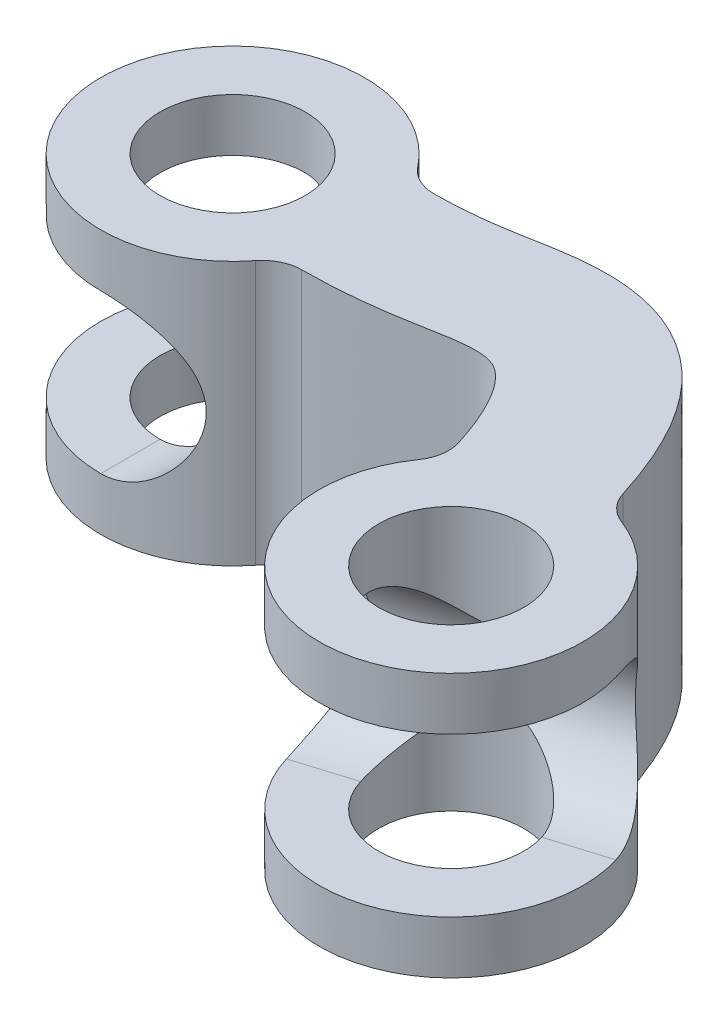
SolidWorks part; units mm, degrees
ref_plane "Front Plane" through (0, 0, 0) normal (0, 0, 1) x (1, 0, 0)
ref_plane "Top Plane" through (0, 0, 0) normal (0, 1, 0) x (1, 0, 0)
ref_plane "Right Plane" through (0, 0, 0) normal (1, 0, 0) x (0, 0, -1)
sketch "Sketch5" plane through (0, 0, 0) normal (0, 1, 0) x (1, 0, 0)
  line L0 (0, 0) -> (20, 0) construction
  line L1 (18.2322, -1.7678) -> (14.6967, 1.7678) construction
  line L2 (0, 0) -> (5, 0) construction
  line L3 (18.7059, 4.8296) -> (18.2322, 5.3033)
  line L4 (15.1704, 1.2941) -> (14.6967, 1.7678)
  line L5 (5, 2.5) -> (4.3301, 2.5)
  line L6 (5, -2.5) -> (4.3301, -2.5)
  line L7 (21.7678, 1.7678) -> (18.2322, 5.3033) construction
  line L8 (20, 0) -> (16.4645, 3.5355) construction
  line L9 (20, 0) -> (16.4645, 3.5355) construction
  line L10 (20, 0) -> (16.4645, -3.5355) construction
  arc A0 (4.3301, 2.5) -> (4.3301, -2.5) centre (0, 0) ccw
  arc A1 (15.1704, 1.2941) -> (18.7059, 4.8296) centre (20, 0) ccw
  spline S0 degree 3 poles (5, 0) (7.2923, 0) (9.8659, 3.8705) (14.4742, 5.5258) (16.4645, 3.5355) knots 0 0 0 0 0.526061 1 1 1 1 construction
  spline S1 degree 1 poles (5, 2.5) (18.2322, 5.3033) knots 0 0 1 1 construction
  spline S2 degree 3 poles (5, 2.5) (5.1773, 2.5) (5.4681, 2.5503) (6.2162, 2.992) (7.2869, 3.9461) (8.6553, 5.2032) (10.471, 6.4596) (12.7733, 7.3462) (15.206, 7.2299) (17.0379, 6.3484) (17.863, 5.6725) (18.2322, 5.3033) knots 0 0 0 0 0.125 0.25 0.375 0.5 0.625 0.75 0.875 0.9375 1 1 1 1
  spline S3 degree 1 poles (5, -2.5) (14.6967, 1.7678) knots 0 0 1 1 construction
  spline S4 degree 3 poles (5, -2.5) (5.4364, -2.5) (6.3305, -2.4036) (7.8897, -1.8868) (9.3956, -0.8905) (10.7305, 0.3262) (11.849, 1.3378) (12.8808, 2.0258) (13.5619, 2.2438) (13.8761, 2.2489) (14.0574, 2.2149) (14.2613, 2.1231) (14.4834, 1.9668) (14.6318, 1.8327) (14.6967, 1.7678) knots 0 0 0 0 0.0625 0.125 0.25 0.375 0.5 0.625 0.75 0.8125 0.875 0.9375 0.96875 1 1 1 1
  dimension "D2" = 10
  dimension "D3" = 10
  dimension "D1" = 20
  dimension "D4" = 5
  dimension "D5" = 2.5
  dimension "D6" = 2.5
  dimension "D7" = 10.5631
  dimension "D8" = 3.4592
  dimension "D9" = 14.6967
  dimension "D10" = 16.4645
  dimension "D11" = 3.5355
  dimension "D12" = 45
  dimension "D13" = 45
extrude "Boss-Extrude3" [suppressed] add sketch "Sketch5" along normal blind 10
sketch "Sketch6" [suppressed] plane through (0, 0, 0) normal (0, 1, 0) x (1, 0, 0)
  circle A0 centre (0, 0) radius 2.75
  circle A1 centre (20, 0) radius 2.75
  arc A2 (4.3301, 2.5) -> (4.3301, -2.5) centre (0, 0) ccw construction
  arc A3 (15.1704, 1.2941) -> (18.7059, 4.8296) centre (20, 0) ccw construction
  dimension "D1" = 5.5
  dimension "D2" = 5.5
extrude "Cut-Extrude3" [suppressed] cut sketch "Sketch6" along normal up to next
sketch "Sketch8" [suppressed] plane through (0, 0, 0) normal (0, 0, 1) x (1, 0, 0)
  line L0 (0, 0) -> (0, 10) construction
  line L1 (2.75, 10) -> (-2.75, 10) construction
  line L2 (20, 0) -> (20, 10) construction
  line L3 (15, 0) -> (25, 0) construction
  line L4 (22.75, 10) -> (17.25, 10) construction
  line L5 (0, 8) -> (-5, 8)
  line L6 (-5, 10) -> (-5, 0) construction
  line L7 (0, 2) -> (-5, 2)
  line L8 (-5, 2) -> (-5, 8)
  line L9 (20, 8) -> (25, 8) construction
  line L12 (25, 8) -> (25, 2) construction
  line L13 (25, 0) -> (25, 10) construction
  line L14 (25, 2) -> (20, 2) construction
  arc A0 (0, 2) -> (0, 8) centre (0, 5) ccw
  arc A1 (20, 8) -> (20, 2) centre (20, 5) ccw construction
  point P23 (0, 0)
  dimension "D1" = 6
  dimension "D2" = 6
extrude "Cut-Extrude4" [suppressed] cut sketch "Sketch8" against normal up to next and the other way up to next
ref_plane "Plane1" [suppressed] through (20, 0, 0) normal (-0.7071, 0, 0.7071) x (0.7071, 0, 0.7071)
sketch "Sketch9" [suppressed] plane through (20, 0, 0) normal (-0.7071, 0, 0.7071) x (0.7071, 0, 0.7071)
  line L0 (0, 10) -> (0, 0) construction
  line L1 (2.75, 10) -> (-2.75, 10) construction
  line L2 (0, 0) -> (-5, 0) construction
  line L3 (0, 8) -> (5, 8)
  line L4 (5, 0) -> (5, 10) construction
  line L5 (5, 8) -> (5, 2)
  line L6 (5, 2) -> (0, 2)
  arc A0 (0, 8) -> (0, 2) centre (0, 5) ccw
  dimension "D1" = 3
extrude "Cut-Extrude5" [suppressed] cut sketch "Sketch9" against normal up to next and the other way up to next
fillet "Fillet2" [suppressed] radius 1.5
sketch "Sketch10" plane through (0, 0, 0) normal (0, 1, 0) x (1, 0, 0)
  line L0 (0, 0) -> (17.664, -9.38) construction
  line L1 (0, 0) -> (20, 0) construction
  line L2 (17.664, -9.38) -> (16.1996, -4.5993) construction
  line L3 (17.664, -9.38) -> (12.8832, -10.8444) construction
  line L4 (0, 0) -> (5, 0) construction
  line L10 (4.3301, -2.5) -> (5, -2.5)
  line L11 (4.3301, 2.5) -> (5, 2.5)
  line L12 (0, 2.5) -> (5, 2.5) construction
  line L13 (0, -2.5) -> (5, -2.5) construction
  line L14 (13.8092, -5.3315) -> (14.0054, -5.972)
  line L15 (18.5899, -3.8671) -> (18.7861, -4.5075)
  arc A2 (4.3301, 2.5) -> (4.3301, -2.5) centre (0, 0) ccw
  arc A3 (14.0054, -5.972) -> (18.7861, -4.5075) centre (17.664, -9.38) ccw
  spline S0 degree 3 poles (5, 0) (7.6511, 0) (10.839, 1.1812) (14.6985, 0.301) (16.1996, -4.5993) knots 0 0 0 0 0.408335 1 1 1 1 construction
  spline S1 degree 1 poles (5, -2.5) (13.8092, -5.3315) knots 0 0 1 1 construction
  spline S2 degree 3 poles (5, -2.5) (5.2187, -2.5) (5.6664, -2.4937) (6.4776, -2.4588) (7.3991, -2.3789) (8.3495, -2.2467) (9.4283, -2.0559) (10.4107, -1.8667) (11.2578, -1.8216) (11.7589, -1.9336) (12.1217, -2.1363) (12.5696, -2.6179) (12.9624, -3.2123) (13.3175, -3.9467) (13.5984, -4.6772) (13.7439, -5.1183) (13.8092, -5.3315) knots 0 0 0 0 0.03125 0.0625 0.125 0.1875 0.25 0.375 0.5 0.625 0.75 0.8125 0.875 0.9375 0.96875 1 1 1 1
  spline S3 degree 1 poles (5, 2.5) (18.5899, -3.8671) knots 0 0 1 1 construction
  spline S4 degree 3 poles (5, 2.5) (5.1718, 2.5) (5.5262, 2.505) (6.148, 2.5319) (6.8391, 2.5919) (7.5616, 2.6921) (8.4636, 2.85) (9.6258, 3.0779) (11.3942, 3.2332) (13.5777, 2.861) (15.3843, 1.7396) (16.5791, 0.4021) (17.3557, -0.7961) (17.9146, -1.9673) (18.3134, -3.0079) (18.503, -3.5833) (18.5899, -3.8671) knots 0 0 0 0 0.03125 0.0625 0.125 0.1875 0.25 0.375 0.5 0.625 0.75 0.8125 0.875 0.9375 0.96875 1 1 1 1
  dimension "D4" = 10
  dimension "D5" = 10
  dimension "D1" = 20
  dimension "D2" = 20
  dimension "D3" = 27.969
  dimension "D6" = 45
  dimension "D7" = 45
  dimension "D10" = 10.3665
  dimension "D11" = 0.621
  dimension "D12" = 5
  dimension "D13" = 16.1996
  dimension "D8" = 2.5
  dimension "D9" = 2.5
extrude "Boss-Extrude5" add sketch "Sketch10" along normal blind 10
sketch "Sketch17" plane through (0, 0, 0) normal (0, 1, 0) x (1, 0, 0)
  circle A0 centre (0, 0) radius 2.75
  circle A1 centre (17.664, -9.38) radius 2.75
  arc A3 (4.3301, 2.5) -> (4.3301, -2.5) centre (0, 0) ccw construction
  arc A4 (14.0054, -5.972) -> (18.7861, -4.5075) centre (17.664, -9.38) ccw construction
  dimension "D1" = 5.5
extrude "Cut-Extrude9" cut sketch "Sketch17" along normal up to next
ref_plane "Plane3" through (17.664, 0, 9.38) normal (-0.9561, 0, 0.2929) x (0.2929, 0, 0.9561)
sketch "Sketch18" plane through (0, 0, 0) normal (0, 0, 1) x (1, 0, 0)
  line L0 (0, 0) -> (0, 10) construction
  line L1 (2.75, 10) -> (-2.75, 10) construction
  line L2 (0, 8) -> (-5, 8)
  line L3 (-5, 10) -> (-5, 0) construction
  line L4 (-5, 8) -> (-5, 2)
  line L5 (-5, 2) -> (0, 2)
  arc A0 (0, 8) -> (0, 2) centre (0, 5) cw
  dimension "D1" = 3
sketch "Sketch19" plane through (17.664, 0, 9.38) normal (-0.9561, 0, 0.2929) x (0.2929, 0, 0.9561)
  line L0 (0, 0) -> (0, 10) construction
  line L1 (-4.3301, 0) -> (5, 0) construction
  line L2 (2.75, 10) -> (-2.75, 10) construction
  line L3 (0, 8) -> (5, 8)
  line L4 (5, 0) -> (5, 10) construction
  line L5 (5, 8) -> (5, 2)
  line L6 (5, 2) -> (0, 2)
  arc A0 (0, 8) -> (0, 2) centre (0, 5) ccw
  dimension "D1" = 3
extrude "Cut-Extrude10" cut sketch "Sketch18" against normal up to next and the other way up to next
extrude "Cut-Extrude11" cut sketch "Sketch19" against normal up to next and the other way up to next
fillet "Fillet4" radius 1.5 4 edges at (18.7861, 5, 4.5075) (4.3301, 5, -2.5) (4.3301, 5, 2.5) (14.0054, 5, 5.972)
